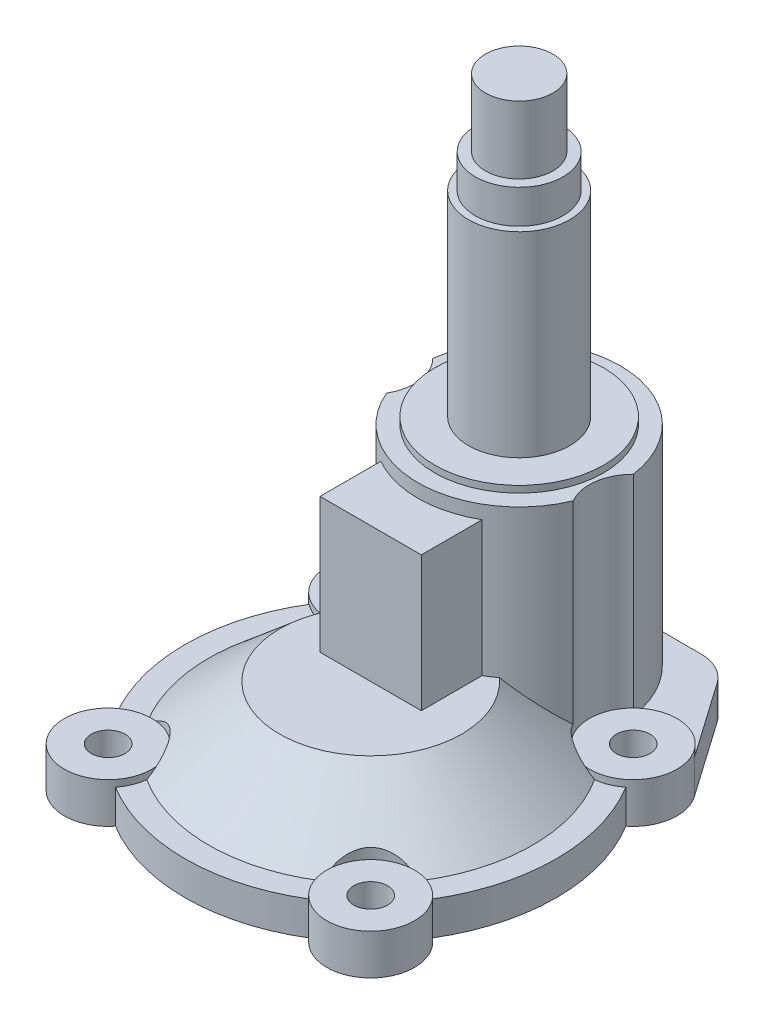
SolidWorks part; units mm, degrees
ref_plane "Front Plane" through (0, 0, 0) normal (0, 0, 1) x (1, 0, 0)
ref_plane "Top Plane" through (0, 0, 0) normal (0, 1, 0) x (1, 0, 0)
ref_plane "Right Plane" through (0, 0, 0) normal (1, 0, 0) x (0, 0, -1)
sketch "Sketch1" plane through (0, 0, 0) normal (0, 1, 0) x (1, 0, 0)
  circle A0 centre (0, 0) radius 27.5
  dimension "D1" = 55
extrude "Boss-Extrude1" add sketch "Sketch1" along normal blind 5
sketch "Sketch3" plane through (0, 0, 0) normal (0, 1, 0) x (1, 0, 0)
  line L0 (0, 0) -> (-19.4454, -19.4454) construction
  line L1 (0, 0) -> (0, -8.3641) construction
  circle A0 centre (-19.4454, -19.4454) radius 6.5
  circle A1 centre (0, 0) radius 27.5
  circle A2 centre (0, 0) radius 27.5
  circle A3 centre (-19.4454, -19.4454) radius 2.5
  circle A4 centre (-19.4454, 19.4454) radius 2.5
  circle A5 centre (-19.4454, 19.4454) radius 6.5
  circle A6 centre (19.4454, 19.4454) radius 2.5
  circle A7 centre (19.4454, 19.4454) radius 6.5
  circle A8 centre (19.4454, -19.4454) radius 2.5
  circle A9 centre (19.4454, -19.4454) radius 6.5
  point P19 (0, 0)
  dimension "D2" = 5
  dimension "D3" = 13
  dimension "D4" = 45
  dimension "D1" = 0
  dimension "D5" = 4
extrude "Cut-Extrude1" cut sketch "Sketch3" against normal through all both and the other way through all contours A2 A3 | A2 A6 | A2 A4 | A8 region at (-18.6809, 0, 18.6809) region at (-18.6809, 0, -18.6809) region at (18.6809, 0, -18.6809)
extrude "Boss-Extrude2" add sketch "Sketch3<3>" along normal blind 6 contours A3 A2 A0 | A3 A2 A0 | A2 A9 A8 | A2 A9 A8 | A2 A7 A6 | A2 A7 A6 | A2 A5 A4 | A2 A5 A4 region at (-17.1693, 0, 17.1693) region at (-21.4818, 0, 21.4818) region at (-21.4818, 0, -21.4818) region at (-17.1693, 0, -17.1693) region at (17.1693, 0, 17.1693) region at (21.4818, 0, 21.4818) region at (21.4818, 0, -21.4818) region at (17.1693, 0, -17.1693)
sketch "Sketch3<3>" plane through (0, 0, 0) normal (0, 1, 0) x (1, 0, 0) same geometry as "Sketch3"
sketch "Sketch4" plane through (0, 0, 0) normal (0, 0, 1) x (1, 0, 0)
  line L0 (0, 5) -> (-24, 5)
  line L1 (14.3383, 5) -> (-14.3383, 5) construction
  line L3 (0, 14) -> (-13.5, 14)
  line L4 (-13.5, 14) -> (-24, 5)
  line L5 (0, 14) -> (0, 5)
  dimension "D1" = 24
  dimension "D2" = 9
  dimension "D3" = 13.5
revolve "Revolve1" add sketch "Sketch4" angle 360 about L5
sketch "Sketch5" plane through (0, 6, 0) normal (0, 1, 0) x (1, 0, 0)
  circle A0 centre (19.4454, -19.4454) radius 6.5
  circle A1 centre (19.4454, 19.4454) radius 6.5
  circle A2 centre (-19.4454, 19.4454) radius 6.5
  circle A3 centre (-19.4454, -19.4454) radius 6.5
extrude "Cut-Extrude2" cut sketch "Sketch5" along normal blind 6
sketch "Sketch6" plane through (0, 5, 0) normal (0, 1, 0) x (1, 0, 0)
  arc A0 (14.8591, 24.0514) -> (-14.8591, 24.0514) centre (0, 22) ccw
  arc A2 (18.7858, 12.979) -> (12.979, 18.7858) centre (19.4454, 19.4454) ccw construction
  arc A3 (12.979, 18.7858) -> (18.7858, 12.979) centre (19.4454, 19.4454) ccw construction
  arc A4 (-12.979, 18.7858) -> (-18.7858, 12.979) centre (-19.4454, 19.4454) ccw construction
  arc A5 (-18.7858, 12.979) -> (-12.979, 18.7858) centre (-19.4454, 19.4454) ccw construction
  arc A6 (14.8591, 24.0514) -> (12.979, 18.7858) centre (19.4454, 19.4454) ccw
  arc A7 (12.979, 18.7858) -> (13.825, 16.1803) centre (19.4454, 19.4454) ccw
  arc A8 (-12.979, 18.7858) -> (-14.8591, 24.0514) centre (-19.4454, 19.4454) ccw
  arc A9 (-13.825, 16.1803) -> (-12.979, 18.7858) centre (-19.4454, 19.4454) ccw
  arc A10 (-13.825, 16.1803) -> (13.825, 16.1803) centre (0, 22) ccw
  point P12 (0, 22)
  dimension "D1" = 30
  dimension "D2" = 22
extrude "Boss-Extrude3" add sketch "Sketch6" along normal blind 31
sketch "Sketch7" plane through (0, 36, 0) normal (0, 1, 0) x (1, 0, 0)
  circle A0 centre (0, 22) radius 12.5
  dimension "D1" = 25
extrude "Boss-Extrude4" add sketch "Sketch7" along normal blind 1
sketch "Sketch8" plane through (0, 37, 0) normal (0, 1, 0) x (1, 0, 0)
  circle A0 centre (0, 22) radius 7.5
  dimension "D1" = 15
extrude "Boss-Extrude5" add sketch "Sketch8" along normal blind 29
sketch "Sketch9" plane through (0, 66, 0) normal (0, 1, 0) x (1, 0, 0)
  circle A0 centre (0, 22) radius 6.5
  dimension "D1" = 13
extrude "Boss-Extrude6" add sketch "Sketch9" along normal blind 5
sketch "Sketch10" plane through (0, 71, 0) normal (0, 1, 0) x (1, 0, 0)
  circle A0 centre (0, 22) radius 5
  dimension "D1" = 10
extrude "Boss-Extrude7" add sketch "Sketch10" along normal blind 10
sketch "Sketch12" plane through (0, 0, 0) normal (0, 1, 0) x (1, 0, 0)
  line L0 (24.7699, 23.1737) -> (16.8801, 34.4415)
  line L1 (11.9652, 37) -> (0, 37)
  line L2 (19.4454, 19.4454) -> (19.4454, 29.703) construction
  arc A0 (18.7858, 12.979) -> (14.8591, 24.0514) centre (19.4454, 19.4454) ccw construction
  arc A1 (14.8591, 24.0514) -> (-14.8591, 24.0514) centre (0, 22) ccw construction
  arc A2 (16.8801, 34.4415) -> (11.9652, 37) centre (11.9652, 31) ccw
  arc A7 (24.7699, 23.1737) -> (14.8591, 24.0514) centre (19.4454, 19.4454) ccw
  arc A14 (14.3383, 23.4662) -> (-14.3383, 23.4662) centre (0, 0) ccw
  arc A17 (-13.825, 16.1803) -> (-14.8591, 24.0514) centre (-19.4454, 19.4454) ccw
  arc A18 (-13.825, 16.1803) -> (13.825, 16.1803) centre (0, 22) ccw
  arc A19 (14.8591, 24.0514) -> (13.825, 16.1803) centre (19.4454, 19.4454) ccw
  arc A20 (14.8591, 24.0514) -> (-14.8591, 24.0514) centre (0, 22) ccw
  arc A21 (-14.3383, 23.4662) -> (-14.8591, 24.0514) centre (-19.4454, 19.4454) ccw
  arc A23 (14.8591, 24.0514) -> (14.3383, 23.4662) centre (19.4454, 19.4454) ccw
  arc A24 (0, 37) -> (-14.8591, 24.0514) centre (0, 22) ccw
  dimension "D2" = 6
  dimension "D1" = 35
  dimension "D3" = 0
extrude "Boss-Extrude11" add sketch "Sketch12" along normal up to surface (5 mm away) up to face at (23.8342, 5, 0)
sketch "Sketch13" plane through (0, 14, 0) normal (0, 1, 0) x (1, 0, 0)
  line L0 (0, 0) -> (0, 4.2576) construction
  line L1 (-7.5, 11.8999) -> (7.5, 11.8999)
  line L2 (-7.5, 11.8999) -> (-7.5, 0)
  line L3 (-7.5, 0) -> (7.5, 0)
  line L4 (7.5, 11.8999) -> (7.5, 0)
  dimension "D1" = 15
extrude "Boss-Extrude12" add sketch "Sketch13" along normal blind 20 contours L2 L1 L4 L3
